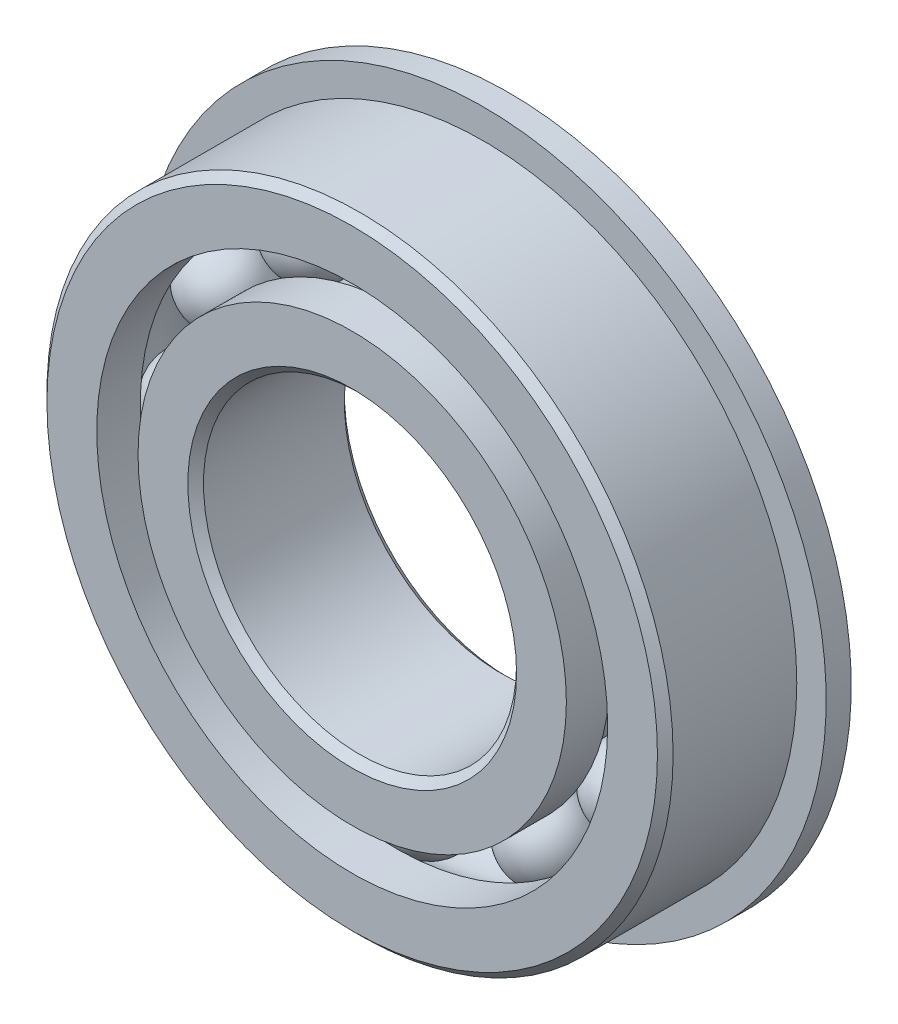
SolidWorks part; units mm, degrees
ref_plane "Front Plane" through (0, 0, 0) normal (0, 0, 1) x (1, 0, 0)
ref_plane "Top Plane" through (0, 0, 0) normal (0, 1, 0) x (1, 0, 0)
ref_plane "Right Plane" through (0, 0, 0) normal (1, 0, 0) x (0, 0, -1)
sketch "Sketch1" plane through (0, 0, 0) normal (1, 0, 0) x (0, 0, -1)
  line L0 (-1.5875, 0) -> (1.5875, 0) construction
  line L1 (0, 6.35) -> (0, -6.35) construction
  line L2 (1.4287, 6.35) -> (-1.4288, 6.35)
  line L3 (-1.4288, 6.35) -> (-1.5875, 6.1913)
  line L4 (-1.5875, 6.1913) -> (-1.5875, 5.1812)
  line L5 (-1.5875, 5.1812) -> (-0.7056, 5.1812)
  line L6 (1.5875, 5.1812) -> (0.7056, 5.1812)
  line L7 (1.5875, 6.1913) -> (1.5875, 5.1812)
  line L8 (1.4287, 6.35) -> (1.5875, 6.1913)
  line L9 (0, 6.35) -> (0, 4.7625) construction
  line L10 (0, 4.7625) -> (0, 3.175) construction
  arc A0 (-0.7056, 5.1812) -> (0.7056, 5.1812) centre (0, 4.7625) cw
  point P14 (0, 3.175)
  dimension "D3" = 1.4111
  dimension "D1" = 45
  dimension "Width" = 3.175
  dimension "OD" = 12.7
  dimension "D2" = 0.1588
  dimension "Shaft Dia" = 6.35
  dimension "D4" = 0.4187
revolve "Revolve1" add sketch "Sketch1" angle 360 about L0
sketch "Sketch3" plane through (0, 0, 0) normal (1, 0, 0) x (0, 0, -1)
  line L0 (-1.5875, 4.3438) -> (-0.7056, 4.3438)
  line L1 (0, 6.35) -> (0, -6.35) construction
  line L2 (-1.5875, 6.1913) -> (-1.5875, 5.1812) construction
  line L3 (-1.5875, 4.3438) -> (-1.5875, 3.3337)
  line L4 (-1.4288, 6.35) -> (-1.5875, 6.1913) construction
  line L5 (-1.5875, 3.3337) -> (-1.4288, 3.175)
  line L6 (-1.4288, 3.175) -> (1.4287, 3.175)
  line L7 (1.4287, 6.35) -> (1.4287, -6.35) construction
  line L8 (1.4287, 3.175) -> (1.5875, 3.3337)
  line L9 (1.5875, -6.1913) -> (1.5875, 6.1913) construction
  line L10 (1.5875, 3.3337) -> (1.5875, 4.3438)
  line L11 (1.5875, 4.3438) -> (0.7056, 4.3438)
  line L13 (1.4287, 6.35) -> (1.5875, 6.1913) construction
  arc A0 (0.7056, 5.1812) -> (-0.7056, 5.1812) centre (0, 4.7625) ccw construction
  arc A1 (0.7056, 4.3438) -> (-0.7056, 4.3438) centre (0, 4.7625) cw
revolve "Revolve3" add sketch "Sketch3" angle 360 about L0
sketch "Sketch4" plane through (0, 0, 0) normal (1, 0, 0) x (0, 0, -1)
  line L0 (-0.8204, 4.7625) -> (0.8204, 4.7625)
  arc A2 (-0.8204, 4.7625) -> (0.8204, 4.7625) centre (0, 4.7625) cw
  arc A3 (0.7056, 5.1812) -> (-0.7056, 5.1812) centre (0, 4.7625) ccw construction
revolve "Revolve4" add sketch "Sketch4" angle 360 about L0
ref_axis "Axis1" through (0, 0, -1.5875) along (0, 0, 1)
pattern_circular "CirPattern1" count 12 every 30 about axis through (0, 0, -1.5875) along (0, 0, 1) of bodies 104
sketch "Sketch5" plane through (0, 0, 0) normal (1, 0, 0) x (0, 0, -1)
  line L0 (-1.5875, 5.1812) -> (-0.7056, 5.1812) construction
  line L1 (-1.5081, 5.1812) -> (-0.8204, 5.1812)
  line L2 (-1.5081, 5.1812) -> (-1.5081, 4.3438)
  line L3 (-1.5081, 4.3438) -> (-0.8204, 4.3438)
  line L4 (-0.8204, 5.1812) -> (-0.8204, 4.3438)
  line L5 (-1.5875, 4.3438) -> (-0.7056, 4.3438) construction
  line L6 (1.5875, 5.1812) -> (0.7056, 5.1812) construction
  line L7 (1.5081, 5.1812) -> (0.8204, 5.1812)
  line L8 (1.5081, 5.1812) -> (1.5081, 4.3438)
  line L9 (1.5081, 4.3438) -> (0.8204, 4.3438)
  line L10 (0.8204, 5.1812) -> (0.8204, 4.3438)
  line L11 (1.5875, 4.3438) -> (0.7056, 4.3438) construction
  line L12 (-1.4288, 6.35) -> (-1.5875, 6.1913) construction
  point P18 (-1.5081, 6.2706)
revolve "Revolve5" [suppressed] add sketch "Sketch5" angle 360 about L0
sketch "Sketch6" plane through (0, 0, 0) normal (1, 0, 0) x (0, 0, -1)
  line L0 (1.5875, 0) -> (-1.5875, 0) construction
  line L1 (1.5875, 5.1812) -> (1.0795, 5.1812)
  line L2 (1.5875, 5.1812) -> (1.5875, 6.9469)
  line L3 (1.5875, 6.9469) -> (1.0795, 6.9469)
  line L4 (1.0795, 5.1812) -> (1.0795, 6.9469)
  dimension "Th" = 0.508
  dimension "Flange OD" = 13.8938
revolve "Revolve6" add sketch "Sketch6" angle 360 about L0
equation "\"D2@Sketch1\" = \"Width@Sketch1\"*.05"
equation "\"D3@Sketch1\" = \"Width@Sketch1\"/2.25"
equation "\"D4@Sketch1\" = (((\"OD@Sketch1\"-\"Width@Sketch1\")/2)/3.25)/3.5"
equation "\"D2@CirPattern1\" = 360/\"Balls@CirPattern1\""
